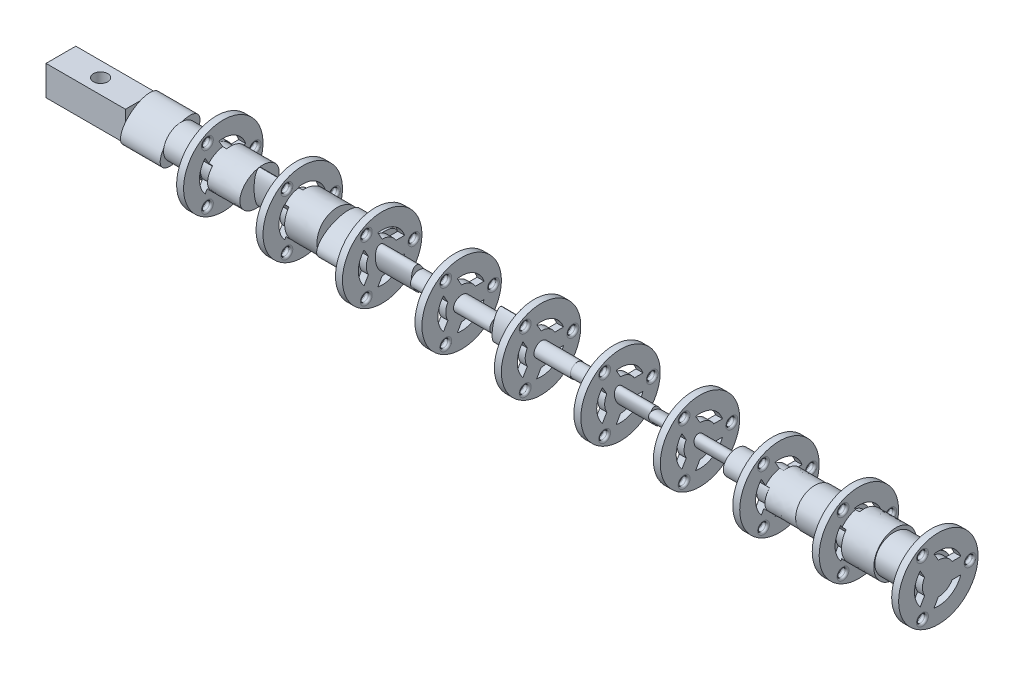
SolidWorks part; units mm, degrees
ref_plane "Front Plane" through (0, 0, 0) normal (0, 0, 1) x (1, 0, 0)
ref_plane "Top Plane" through (0, 0, 0) normal (0, 1, 0) x (1, 0, 0)
ref_plane "Right Plane" through (0, 0, 0) normal (1, 0, 0) x (0, 0, -1)
sketch "Sketch28" plane through (0, 0, 0) normal (1, 0, 0) x (0, 0, -1)
  line L0 (0, 0) -> (0, 30) construction
  line L1 (0, 0) -> (-30, 0) construction
  line L2 (19.0774, 0) -> (-19.0774, 0) construction
  dimension "D1" = 30
sketch "Sketch1" plane through (0, 0, 0) normal (1, 0, 0) x (0, 0, -1)
  line L0 (-1.9461, 2.6508) -> (0, 0) construction
  line L1 (0, 0) -> (-4.612, -3.386) construction
  line L2 (0, 0) -> (0, 30) construction
  ellipse E0 centre (0, 0) end of major axis (-4.612, -3.386) minor radius 3.2884
  dimension "ry_1" = 3.2884
  dimension "rz_1" = 5.7215
  dimension "phi_1" = 36.285
extrude "Boss-Extrude1" add sketch "Sketch1" along normal blind 10
ref_plane "Plane1" through (10, 0, 0) normal (1, 0, 0) x (0, 0, -1)
sketch "Sketch2" plane through (10, 0, 0) normal (1, 0, 0) x (0, 0, -1)
  line L0 (0, 0) -> (-1.6, 3.5278) construction
  line L1 (0, 0) -> (-3.8455, -1.7441) construction
  line L3 (0, 0) -> (0, 30) construction
  ellipse E0 centre (0, 0) end of major axis (3.8455, 1.7441) minor radius 3.8736
  dimension "phi_2" = 24.396
  dimension "ry_2" = 3.8736
  dimension "rz_2" = 4.2225
extrude "Boss-Extrude2" add sketch "Sketch2" along normal blind 10
ref_plane "Plane2" through (20, 0, 0) normal (1, 0, 0) x (0, 0, -1)
sketch "Sketch3" plane through (20, 0, 0) normal (1, 0, 0) x (0, 0, -1)
  line L0 (0, 0) -> (-1.7572, 3.7363) construction
  line L1 (0, 0) -> (-4.628, -2.1766) construction
  line L2 (0, 0) -> (0, 30) construction
  ellipse E0 centre (0, 0) end of major axis (-4.628, -2.1766) minor radius 4.1289
  dimension "ry_3" = 4.1289
  dimension "rz_3" = 5.1143
  dimension "phi_3" = 25.188
extrude "Boss-Extrude3" add sketch "Sketch3" along normal blind 10
ref_plane "Plane3" through (30, 0, 0) normal (1, 0, 0) x (0, 0, -1)
sketch "Sketch4" plane through (30, 0, 0) normal (1, 0, 0) x (0, 0, -1)
  line L0 (-0.0906, 4.2201) -> (0, 0) construction
  line L1 (0, 0) -> (-1.3773, -0.0296) construction
  line L2 (0, 0) -> (0, 30) construction
  ellipse E0 centre (0, 0) end of major axis (-0.0906, 4.2201) minor radius 1.3776
  dimension "ry_4" = 4.2211
  dimension "rz_4" = 1.3776
  dimension "phi_4" = 1.229
extrude "Boss-Extrude4" add sketch "Sketch4" along normal blind 10
ref_plane "Plane4" through (40, 0, 0) normal (1, 0, 0) x (0, 0, -1)
sketch "Sketch5" plane through (40, 0, 0) normal (1, 0, 0) x (0, 0, -1)
  line L0 (-3.4689, 4.7181) -> (0, 0) construction
  line L1 (0, 0) -> (-4.3301, -3.1837) construction
  line L2 (0, 0) -> (0, 30) construction
  ellipse E0 centre (0, 0) end of major axis (3.4689, -4.7181) minor radius 5.3745
  dimension "ry_5" = 5.8561
  dimension "rz_5" = 5.3745
  dimension "phi_5" = 36.325
extrude "Boss-Extrude5" add sketch "Sketch5" along normal blind 10
ref_plane "Plane5" through (50, 0, 0) normal (1, 0, 0) x (0, 0, -1)
sketch "Sketch6" plane through (50, 0, 0) normal (1, 0, 0) x (0, 0, -1)
  line L0 (-1.183, 2.9409) -> (0, 0) construction
  line L1 (0, 0) -> (-5.4902, -2.2085) construction
  line L2 (0, 0) -> (0, 30) construction
  ellipse E0 centre (0, 0) end of major axis (-5.4902, -2.2085) minor radius 3.1699
  dimension "ry_6" = 3.1699
  dimension "rz_6" = 5.9177
  dimension "phi_6" = 21.913
extrude "Boss-Extrude6" add sketch "Sketch6" along normal blind 10
ref_plane "Plane6" through (60, 0, 0) normal (1, 0, 0) x (0, 0, -1)
sketch "Sketch7" plane through (60, 0, 0) normal (1, 0, 0) x (0, 0, -1)
  line L0 (-0.6753, 3.1477) -> (0, 0) construction
  line L1 (0, 0) -> (-1.5989, -0.343) construction
  line L2 (0, 0) -> (0, 30) construction
  ellipse E0 centre (0, 0) end of major axis (0.6753, -3.1477) minor radius 1.6353
  dimension "ry_7" = 3.2193
  dimension "rz_7" = 1.6353
  dimension "phi_7" = 12.109
extrude "Boss-Extrude7" add sketch "Sketch7" along normal blind 10
ref_plane "Plane7" through (70, 0, 0) normal (1, 0, 0) x (0, 0, -1)
sketch "Sketch8" plane through (70, 0, 0) normal (1, 0, 0) x (0, 0, -1)
  line L0 (-0.6248, 1.6084) -> (0, 0) construction
  line L1 (0, 0) -> (-1.897, -0.7369) construction
  line L2 (0, 0) -> (0, 30) construction
  ellipse E0 centre (0, 0) end of major axis (1.897, 0.7369) minor radius 1.7255
  dimension "ry_8" = 1.7255
  dimension "rz_8" = 2.0351
  dimension "phi_8" = 21.228
extrude "Boss-Extrude8" add sketch "Sketch8" along normal blind 10
ref_plane "Plane8" through (80, 0, 0) normal (1, 0, 0) x (0, 0, -1)
sketch "Sketch9" plane through (80, 0, 0) normal (1, 0, 0) x (0, 0, -1)
  line L0 (-0.1872, 1.814) -> (0, 0) construction
  line L1 (0, 0) -> (-2.0263, -0.2091) construction
  line L2 (0, 0) -> (0, 30) construction
  ellipse E0 centre (0, 0) end of major axis (-2.0263, -0.2091) minor radius 1.8236
  dimension "ry_9" = 1.8236
  dimension "rz_9" = 2.037
  dimension "phi_9" = 5.893
extrude "Boss-Extrude9" add sketch "Sketch9" along normal blind 10
ref_plane "Plane9" through (90, 0, 0) normal (1, 0, 0) x (0, 0, -1)
sketch "Sketch10" plane through (90, 0, 0) normal (1, 0, 0) x (0, 0, -1)
  line L0 (-1.2624, 0.2629) -> (0, 0) construction
  line L1 (0, 0) -> (-0.7396, -3.5516) construction
  line L2 (0, 0) -> (0, 30) construction
  ellipse E0 centre (0, 0) end of major axis (-0.7396, -3.5516) minor radius 1.2895
  dimension "ry_10" = 1.2895
  dimension "rz_10" = 3.6278
  dimension "phi_10" = 78.237
extrude "Boss-Extrude10" add sketch "Sketch10" along normal blind 10
ref_plane "Plane10" through (100, 0, 0) normal (1, 0, 0) x (0, 0, -1)
sketch "Sketch11" plane through (100, 0, 0) normal (1, 0, 0) x (0, 0, -1)
  line L0 (-1.2875, 1.1619) -> (0, 0) construction
  line L1 (0, 0) -> (-1.2367, -1.3704) construction
  line L2 (0, 0) -> (0, 30) construction
  ellipse E0 centre (0, 0) end of major axis (1.2367, 1.3704) minor radius 1.7343
  dimension "ry_11" = 1.7343
  dimension "rz_11" = 1.846
  dimension "phi_11" = 47.936
extrude "Boss-Extrude11" add sketch "Sketch11" along normal blind 10
ref_plane "Plane11" through (110, 0, 0) normal (1, 0, 0) x (0, 0, -1)
sketch "Sketch12" plane through (110, 0, 0) normal (1, 0, 0) x (0, 0, -1)
  line L0 (-0.4588, 1.6909) -> (0, 0) construction
  line L1 (0, 0) -> (-1.6705, -0.4532) construction
  line L2 (0, 0) -> (0, 30) construction
  ellipse E0 centre (0, 0) end of major axis (-0.4588, 1.6909) minor radius 1.7309
  dimension "ry_12" = 1.752
  dimension "rz_12" = 1.7309
  dimension "phi_12" = 15.18
extrude "Boss-Extrude12" add sketch "Sketch12" along normal blind 10
ref_plane "Plane12" through (120, 0, 0) normal (1, 0, 0) x (0, 0, -1)
sketch "Sketch13" plane through (120, 0, 0) normal (1, 0, 0) x (0, 0, -1)
  line L0 (-0.9003, 2.2884) -> (0, 0) construction
  line L1 (0, 0) -> (-1.2458, -0.4901) construction
  line L2 (0, 0) -> (0, 30) construction
  ellipse E0 centre (0, 0) end of major axis (0.9003, -2.2884) minor radius 1.3388
  dimension "ry_13" = 2.4591
  dimension "rz_13" = 1.3388
  dimension "phi_13" = 21.475
extrude "Boss-Extrude13" add sketch "Sketch13" along normal blind 10
ref_plane "Plane13" through (130, 0, 0) normal (1, 0, 0) x (0, 0, -1)
sketch "Sketch14" plane through (130, 0, 0) normal (1, 0, 0) x (0, 0, -1)
  line L0 (-1.9366, 1.284) -> (0, 0) construction
  line L1 (0, 0) -> (-0.7285, -1.0987) construction
  line L2 (0, 0) -> (0, 30) construction
  ellipse E0 centre (0, 0) end of major axis (1.9366, -1.284) minor radius 1.3183
  dimension "ry_14" = 2.3236
  dimension "rz_14" = 1.3183
  dimension "phi_14" = 56.455
extrude "Boss-Extrude14" add sketch "Sketch14" along normal blind 10
ref_plane "Plane14" through (140, 0, 0) normal (1, 0, 0) x (0, 0, -1)
sketch "Sketch15" plane through (140, 0, 0) normal (1, 0, 0) x (0, 0, -1)
  line L0 (-0.9732, 1.6875) -> (0, 0) construction
  line L1 (0, 0) -> (-1.1436, -0.6595) construction
  line L2 (0, 0) -> (0, 30) construction
  ellipse E0 centre (0, 0) end of major axis (0.9732, -1.6875) minor radius 1.3201
  dimension "ry_15" = 1.948
  dimension "rz_15" = 1.3201
  dimension "phi_15" = 29.972
extrude "Boss-Extrude15" add sketch "Sketch15" along normal blind 10
ref_plane "Plane15" through (150, 0, 0) normal (1, 0, 0) x (0, 0, -1)
sketch "Sketch16" plane through (150, 0, 0) normal (1, 0, 0) x (0, 0, -1)
  line L0 (-0.4648, 2.9128) -> (0, 0) construction
  line L1 (0, 0) -> (-3.211, -0.5123) construction
  line L3 (0, 0) -> (0, 30) construction
  ellipse E0 centre (0, 0) end of major axis (-3.211, -0.5123) minor radius 2.9496
  dimension "ry_16" = 2.9496
  dimension "rz_16" = 3.2516
  dimension "phi_16" = 9.066
extrude "Boss-Extrude16" add sketch "Sketch16" along normal blind 10
ref_plane "Plane16" through (160, 0, 0) normal (1, 0, 0) x (0, 0, -1)
sketch "Sketch17" plane through (160, 0, 0) normal (1, 0, 0) x (0, 0, -1)
  line L0 (-1.7714, 3.3798) -> (0, 0) construction
  line L1 (0, 0) -> (-4.2964, -2.2518) construction
  line L2 (0, 0) -> (0, 30) construction
  ellipse E0 centre (0, 0) end of major axis (4.2964, 2.2518) minor radius 3.8158
  dimension "ry_17" = 3.8158
  dimension "rz_17" = 4.8508
  dimension "phi_17" = 27.66
extrude "Boss-Extrude17" add sketch "Sketch17" along normal blind 10
ref_plane "Plane17" through (170, 0, 0) normal (1, 0, 0) x (0, 0, -1)
sketch "Sketch18" plane through (170, 0, 0) normal (1, 0, 0) x (0, 0, -1)
  line L0 (-3.9352, 3.3136) -> (0, 0) construction
  line L1 (0, 0) -> (-3.1548, -3.7466) construction
  line L2 (0, 0) -> (0, 30) construction
  ellipse E0 centre (0, 0) end of major axis (3.9352, -3.3136) minor radius 4.898
  dimension "ry_18" = 5.1445
  dimension "rz_18" = 4.898
  dimension "phi_18" = 49.902
extrude "Boss-Extrude18" add sketch "Sketch18" along normal blind 10
ref_plane "Plane18" through (180, 0, 0) normal (1, 0, 0) x (0, 0, -1)
sketch "Sketch19" plane through (180, 0, 0) normal (1, 0, 0) x (0, 0, -1)
  line L0 (-4.8065, 2.2874) -> (0, 0) construction
  line L1 (0, 0) -> (-2.4105, -5.0653) construction
  line L2 (0, 0) -> (0, 30) construction
  ellipse E0 centre (0, 0) end of major axis (-2.4105, -5.0653) minor radius 5.3231
  dimension "ry_19" = 5.3231
  dimension "rz_19" = 5.6097
  dimension "phi_19" = 64.551
extrude "Boss-Extrude19" add sketch "Sketch19" along normal blind 10
ref_plane "Plane19" through (190, 0, 0) normal (1, 0, 0) x (0, 0, -1)
sketch "Sketch20" plane through (190, 0, 0) normal (1, 0, 0) x (0, 0, -1)
  line L0 (-4.7232, 2.1085) -> (0, 0) construction
  line L1 (0, 0) -> (-1.9329, -4.33) construction
  line L2 (0, 0) -> (0, 30) construction
  ellipse E0 centre (0, 0) end of major axis (-4.7232, 2.1085) minor radius 4.7418
  dimension "ry_20" = 5.1725
  dimension "rz_20" = 4.7418
  dimension "phi_20" = 65.943
extrude "Boss-Extrude20" add sketch "Sketch20" along normal blind 10
sketch "Sketch21" plane through (0, 0, 0) normal (0, 1, 0) x (1, 0, 0)
  line L0 (0, 0) -> (200, 0) construction
  line L1 (19.125, 0) -> (20.875, 0)
  line L2 (19.125, 0) -> (19.125, -10)
  line L3 (19.125, -10) -> (20.875, -10)
  line L4 (20.875, 0) -> (20.875, -10)
  line L5 (200, -5.1035) -> (200, 5.1035) construction
  point P6 (20, -10)
  dimension "D1" = 20
  dimension "D2" = 10
  dimension "D3" = 1.75
revolve "Revolve1" add sketch "Sketch21" angle 360 about L0
sketch "Sketch22" plane through (20.875, 0, 0) normal (1, 0, 0) x (0, 0, -1)
  line L0 (0, 0) -> (-4, 6.9282) construction
  line L1 (0, 0) -> (-4, -6.9282) construction
  line L2 (0, 0) -> (8, 0) construction
  line L3 (22, 0) -> (-22, 0) construction
  line L4 (-4.5605, 3.899) -> (-3.4641, 2)
  line L5 (-3.4641, -2) -> (-4.5605, -3.899)
  line L6 (5.6569, 2) -> (3.4641, 2)
  line L7 (0, 4) -> (-1.0964, 5.899)
  line L8 (-1.0964, -5.899) -> (0, -4)
  line L9 (3.4641, -2) -> (5.6569, -2)
  circle A0 centre (-4, 6.9282) radius 1
  circle A1 centre (-4, -6.9282) radius 1
  circle A2 centre (8, 0) radius 1
  arc A3 (-3.4641, 2) -> (-3.4641, -2) centre (0, 0) ccw
  arc A5 (-4.5605, -3.899) -> (-4.5605, 3.899) centre (0, 0) cw
  arc A7 (-1.0964, 5.899) -> (5.6569, 2) centre (0, 0) cw
  arc A8 (3.4641, 2) -> (0, 4) centre (0, 0) ccw
  arc A9 (5.6569, -2) -> (-1.0964, -5.899) centre (0, 0) cw
  arc A10 (0, -4) -> (3.4641, -2) centre (0, 0) ccw
  point P30 (0, 0)
  dimension "D4" = 2
  dimension "D7" = 6
  dimension "D9" = 4
  dimension "D1" = 120
  dimension "D2" = 120
  dimension "D3" = 8
  dimension "D5" = 2
  dimension "D6" = 2
  dimension "D8" = 3
extrude "Cut-Extrude1" cut sketch "Sketch22" against normal up to surface (1.75 mm away) from offset 1 up to face at (19.125, 1.7441, -3.8455)
fillet "Fillet2" radius 0.5 6 edges at (20.875, -6.9282, 3) (19.125, -6.9282, 5) (20.875, 6.9282, 3) (19.125, 6.9282, 5) (20.875, 0, -9) (19.125, 0, -7)
pattern_linear "LPattern1" count 10 spacing 20 along (1, 0, 0) of "Revolve1", "Cut-Extrude1", "Fillet2"
sketch "Sketch23" plane through (0, 0, 0) normal (-1, 0, 0) x (0, 0, 1)
  line L1 (-3.75, 3.75) -> (3.75, 3.75)
  line L2 (-3.75, 3.75) -> (-3.75, -3.75)
  line L3 (-3.75, -3.75) -> (3.75, -3.75)
  line L4 (3.75, 3.75) -> (3.75, -3.75)
  line L5 (-3.75, 3.75) -> (3.75, -3.75) construction
  line L6 (-3.75, -3.75) -> (3.75, 3.75) construction
  point P0 (0, 0)
  dimension "D1" = 7.5
extrude "Boss-Extrude21" add sketch "Sketch23" along normal blind 20
sketch "Sketch26" plane through (0, -3.75, 0) normal (0, -1, 0) x (-1, 0, 0)
  line L0 (20, 3.75) -> (0, 3.75) construction
  point P0 (10, 0)
  point P7 (10, 3.75)
hole_wizard "M3 Clearance Hole1" positions "Sketch26" profile "Sketch27" hole size "M3" standard "ANSI Metric" end condition up to next
sketch "Sketch27" plane through (-10, -3.75, 0) normal (1, 0, 0) x (0, 0, -1)
  line L0 (0, 0) -> (0, 7.5)
  line L1 (0, 7.5) -> (1.8, 7.5)
  line L2 (1.8, 7.5) -> (1.8, 0)
  line L5 (1.8, 0) -> (0, 0)
  line L11 (0, -6.35) -> (0, 107.95) construction
  dimension "Thru Hole Dia." = 3.6
  dimension "Thru Hole Depth" = 7.5
